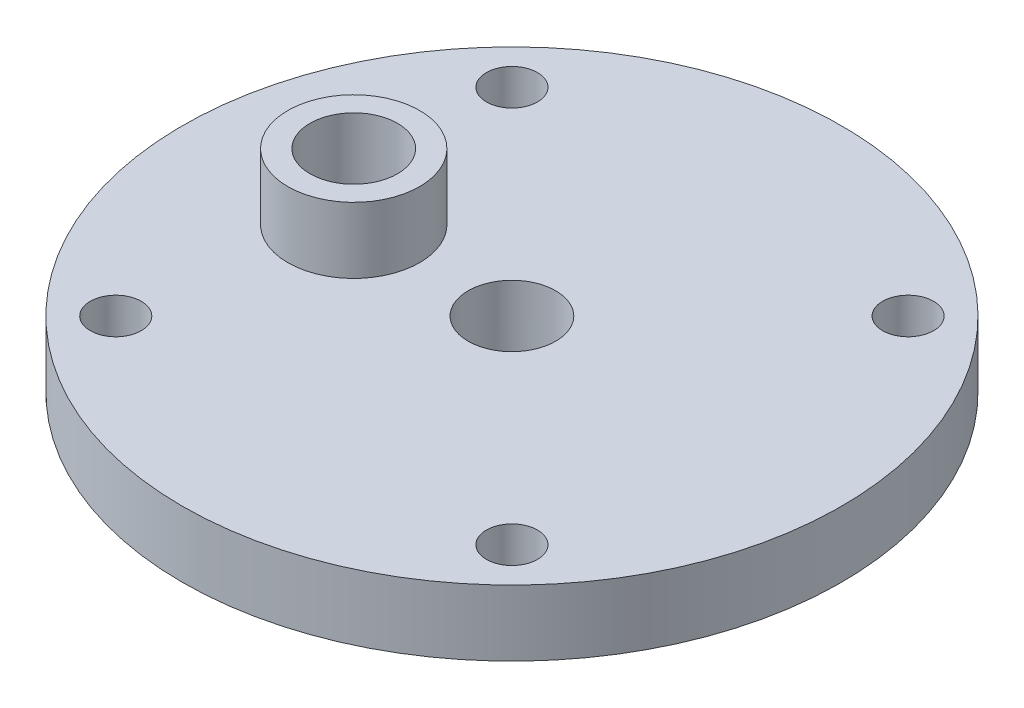
SolidWorks part; units mm, degrees
material "1023 Carbon Steel Sheet (SS)"
ref_plane "Front Plane" through (0, 0, 0) normal (0, 0, 1) x (1, 0, 0)
ref_plane "Top Plane" through (0, 0, 0) normal (0, 1, 0) x (1, 0, 0)
ref_plane "Right Plane" through (0, 0, 0) normal (1, 0, 0) x (0, 0, -1)
ref_axis "Axis1" through (0, 10.0012, 0) along (0, -1, 0)
ref_plane "Plane1" through (0, 0, 0) normal (0, 0, 1) x (0, -1, 0)
sketch "Sketch1" plane through (0, 0, 0) normal (0, 0, 1) x (1, 0, 0)
  line L0 (0, 0) -> (-15.875, 0)
  line L1 (-15.875, 0) -> (-15.875, 3.175)
  line L2 (-15.875, 3.175) -> (-9.525, 3.175)
  line L4 (-15.875, 7.9375) -> (-31.75, 7.9375)
  line L5 (-31.75, 7.9375) -> (-31.75, 14.2875)
  line L6 (-31.75, 14.2875) -> (0, 14.2875)
  line L7 (0, 14.2875) -> (0, 0)
  line L8 (-15.875, 7.9375) -> (-15.875, 6.35)
  line L9 (-15.875, 6.35) -> (-9.525, 6.35)
  line L10 (-9.525, 6.35) -> (-9.525, 3.175)
  point P10 (-15.875, 1.5875)
  dimension "D1" = 15.875
  dimension "D2" = 3.175
  dimension "D4" = 6.35
  dimension "D5" = 31.75
  dimension "D6" = 6.35
  dimension "1/8" = 3.175
  dimension "D7" = 1.5875
revolve "Revolve1" add sketch "Sketch1" angle 360 about L7
hole_wizard "Pipe Tap Drill for 1/8 Tap1" positions "3DSketch1" profile "Sketch2" hole size "1/8" standard "ANSI Inch"
sketch3d "3DSketch1"
  circle A0 centre (0, 14.2875, 0) radius 31.75 construction
  point P0 (0, 14.2875, 0)
  point P5 (0, 46.0375, 0)
sketch "Sketch2" plane through (0, 14.2875, 0) normal (1, 0, 0) x (0, 0, 1)
  line L0 (0, 0) -> (0, 27.9335)
  line L1 (0, 27.9335) -> (4.2164, 25.4)
  line L2 (4.2164, 25.4) -> (4.2164, 0)
  line L5 (4.2164, 0) -> (0, 0)
  line L10 (0, 27.9335) -> (-4.2164, 25.4) construction
  line L11 (0, -6.35) -> (0, 107.95) construction
  dimension "Hole Dia." = 8.4328
  dimension "Hole Depth" = 25.4
  dimension "Drill Angle" = 118
sketch "Sketch3" plane through (0, 0, 0) normal (0, 0, -1) x (-1, 0, 0)
  line L0 (-11.5679, 5.2179) -> (0, -6.35)
  line L1 (-11.3883, 5.3975) -> (-11.7475, 5.0383)
  line L2 (-11.7475, 5.0383) -> (-5.08, -1.6292)
  line L3 (-5.08, -1.6292) -> (-4.7208, -1.27)
  line L4 (-4.7208, -1.27) -> (-11.3883, 5.3975)
  line L5 (0, 0) -> (0, -6.35) construction
  line L6 (-15.875, 0) -> (15.875, 0) construction
  line L7 (-31.75, 7.9375) -> (31.75, 7.9375) construction
  point P4 (-11.5679, 5.2179)
  dimension "D1" = 45
  dimension "D2" = 0.508
  dimension "D3" = 6.35
  dimension "D4" = 1.27
  dimension "D5" = 2.54
revolve "Cut-Revolve2" cut sketch "Sketch3" angle 360 about L0 region at (8.1443, 1.9739, 0)
pattern_circular "CirPattern1" count 4 over 360 about axis through (0, 14.2875, 0) along (0, 1, 0) of "Cut-Revolve2" reverse direction yes
sketch "Sketch5" plane through (0, 14.2875, 0) normal (0, 1, 0) x (1, 0, 0)
  line L0 (-15.24, 0) -> (0, 0) construction
  circle A0 centre (-15.24, 0) radius 6.35
  dimension "D2" = 12.7
  dimension "D1" = 15.24
extrude "Boss-Extrude1" add sketch "Sketch5" along normal blind 6.35
hole_wizard "Pipe Tap Drill for 1/8 Tap2" positions "3DSketch2" profile "Sketch4" hole size "1/8" standard "ANSI Inch"
sketch3d "3DSketch2"
  line L2 (-15.24, 20.6375, 0) -> (0, 20.6375, 0) construction
  circle A0 centre (-15.24, 20.6375, 0) radius 6.35 construction
  point P0 (-15.24, 20.6375, 0)
  point P20 (-15.24, 26.9875, 0)
sketch "Sketch4" plane through (-15.24, 20.6375, 0) normal (1, 0, 0) x (0, 0, 1)
  line L0 (0, 0) -> (0, 8.8835)
  line L1 (0, 8.8835) -> (4.2164, 6.35)
  line L2 (4.2164, 6.35) -> (4.2164, 0)
  line L5 (4.2164, 0) -> (0, 0)
  line L10 (0, 8.8835) -> (-4.2164, 6.35) construction
  line L11 (0, -6.35) -> (0, 107.95) construction
  dimension "Hole Dia." = 8.4328
  dimension "Hole Depth" = 6.35
  dimension "Drill Angle" = 118
hole_wizard "1/8 (0.125) Diameter Hole4" positions "3DSketch3" profile "Sketch7" hole size "1/8" standard "ANSI Inch" end condition up to next
sketch3d "3DSketch3"
  circle A0 centre (-15.24, 20.6375, 0) radius 4.2164 construction
  point P0 (-15.24, 20.6375, 0)
  point P5 (-15.24, 24.8539, 0)
sketch "Sketch7" plane through (-15.24, 20.6375, 0) normal (1, 0, 0) x (0, 0, 1)
  line L0 (0, 0) -> (0, 14.2875)
  line L1 (0, 14.2875) -> (1.5875, 14.2875)
  line L2 (1.5875, 14.2875) -> (1.5875, 0)
  line L5 (1.5875, 0) -> (0, 0)
  line L11 (0, -6.35) -> (0, 107.95) construction
  dimension "Thru Hole Dia." = 3.175
  dimension "Thru Hole Depth" = 14.2875
hole_wizard "#10 (0.1935) Diameter Hole1" positions "3DSketch4" profile "Sketch8" hole size "#10" standard "ANSI Inch" end condition up to next
sketch3d "3DSketch4"
  line L0 (19.083, 14.2875, -19.083) -> (0, 14.2875, 0) construction
  line L1 (0, 14.2875, 0) -> (31.75, 14.2875, 0) construction
  line L3 (19.083, 14.2875, -19.083) -> (22.4506, 14.2875, -22.4506) construction
  circle A0 centre (0, 14.2875, 0) radius 31.75 construction
  point P0 (19.083, 14.2875, -19.083)
  point P8 (0, 46.0375, 0)
  dimension "D1" = 45
  dimension "D2" = 4.7625
sketch "Sketch8" plane through (19.083, 14.2875, -19.083) normal (1, 0, 0) x (0, 0, 1)
  line L0 (0, 0) -> (0, 6.35)
  line L1 (0, 6.35) -> (2.4574, 6.35)
  line L2 (2.4574, 6.35) -> (2.4574, 0)
  line L5 (2.4574, 0) -> (0, 0)
  line L11 (0, -6.35) -> (0, 107.95) construction
  dimension "Thru Hole Dia." = 4.9149
  dimension "Thru Hole Depth" = 6.35
pattern_circular "CirPattern2" count 4 over 360 about axis through (0, 14.2875, 0) along (0, 1, 0) of "#10 (0.1935) Diameter Hole1"
